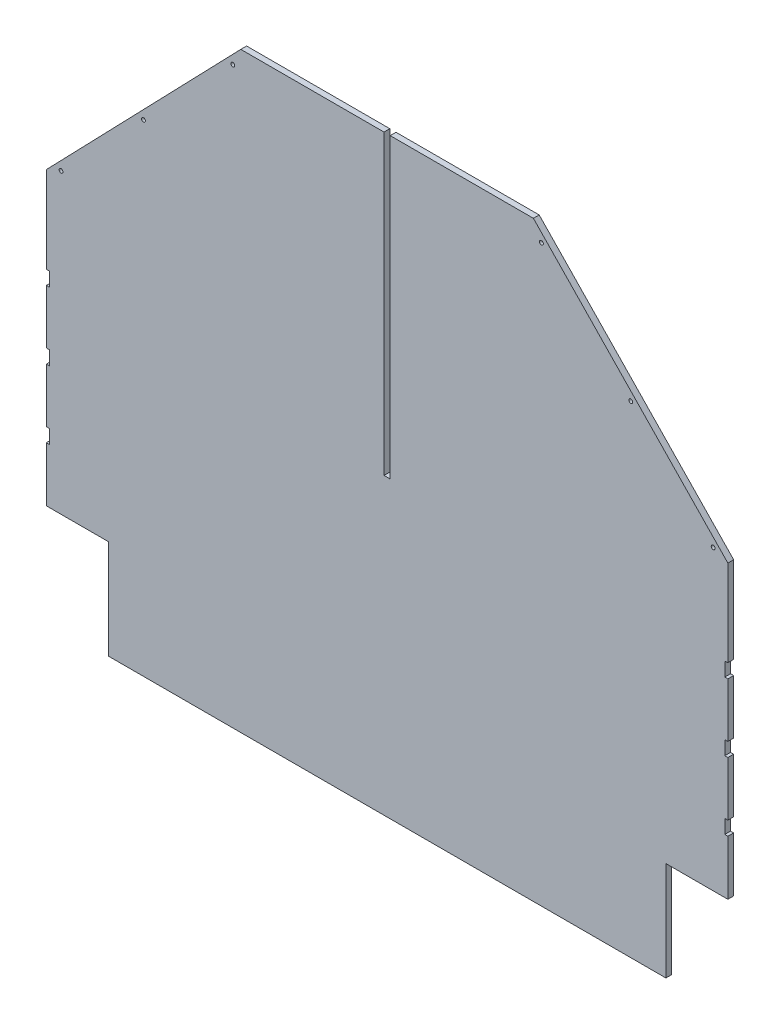
SolidWorks part; units mm, degrees
material "Pine"
ref_plane "Front Plane" through (0, 0, 0) normal (0, 0, 1) x (1, 0, 0)
ref_plane "Top Plane" through (0, 0, 0) normal (0, 1, 0) x (1, 0, 0)
ref_plane "Right Plane" through (0, 0, 0) normal (1, 0, 0) x (0, 0, -1)
sketch "Sketch1" plane through (0, 0, 0) normal (0, 0, 1) x (1, 0, 0)
  line L0 (1068.4674, -524.1043) -> (941.4674, -524.1043)
  line L1 (70.0554, 485.5457) -> (669.8794, 485.5457)
  line L2 (-328.5326, 72.7957) -> (-328.5326, -524.1043)
  line L3 (-201.5326, -727.3043) -> (941.4674, -727.3043)
  line L4 (1068.4674, 72.7957) -> (1068.4674, -524.1043)
  line L5 (-328.5326, -524.1043) -> (-201.5326, -524.1043)
  line L6 (-201.5326, -524.1043) -> (-201.5326, -727.3043)
  line L7 (369.9674, -727.3043) -> (369.9674, -138.7274) construction
  line L8 (-328.5326, -524.1043) -> (-328.5326, 72.7957) construction
  line L9 (-328.5326, 72.7957) -> (70.0554, 485.5457)
  line L10 (941.4674, -524.1043) -> (941.4674, -727.3043)
  line L11 (1068.4674, -524.1043) -> (1068.4674, 72.7957) construction
  line L12 (1068.4674, 72.7957) -> (669.8794, 485.5457)
  line L13 (369.9674, 485.5457) -> (369.9674, -138.7274) construction
  dimension "D2" = 127
  dimension "D3" = 596.9
  dimension "D4" = 127
  dimension "D5" = 596.9
  dimension "D6" = 136
  dimension "D7" = 136
extrude "Boss-Extrude1" add sketch "Sketch1" along normal blind 11.9062
sketch "Sketch2" plane through (0, 0, 11.9062) normal (0, 0, 1) x (1, 0, 0)
  line L0 (369.9674, 485.5457) -> (363.6174, 485.5457) construction
  line L1 (669.8794, 485.5457) -> (70.0554, 485.5457) construction
  line L3 (363.6174, 485.5457) -> (376.3174, 485.5457)
  line L4 (363.6174, 485.5457) -> (363.6174, -124.0543)
  line L5 (363.6174, -124.0543) -> (376.3174, -124.0543)
  line L6 (376.3174, 485.5457) -> (376.3174, -124.0543)
  dimension "D1" = 6.35
  dimension "D2" = 609.6
  dimension "D3" = 12.7
extrude "Cut-Extrude1" cut sketch "Sketch2" against normal through all contours L6 L5 L4 L3
sketch "Sketch3" plane through (0, 0, 11.9062) normal (0, 0, 1) x (1, 0, 0)
  line L0 (-328.5326, 72.7957) -> (-328.5326, -524.1043) construction
  line L1 (-328.5326, -412.1538) -> (-322.1826, -412.1538)
  line L2 (-328.5326, -412.1538) -> (-328.5326, -383.5788)
  line L3 (-328.5326, -383.5788) -> (-322.1826, -383.5788)
  line L4 (-322.1826, -412.1538) -> (-322.1826, -383.5788)
  line L6 (-328.5326, -272.4538) -> (-322.1826, -272.4538)
  line L7 (-328.5326, -272.4538) -> (-328.5326, -243.8788)
  line L8 (-328.5326, -243.8788) -> (-322.1826, -243.8788)
  line L9 (-322.1826, -272.4538) -> (-322.1826, -243.8788)
  line L10 (-328.5326, -132.7538) -> (-322.1826, -132.7538)
  line L11 (-328.5326, -132.7538) -> (-328.5326, -104.1788)
  line L12 (-328.5326, -104.1788) -> (-322.1826, -104.1788)
  line L13 (-322.1826, -132.7538) -> (-322.1826, -104.1788)
  line L14 (-322.1826, -397.8663) -> (-324.6647, -397.8663) construction
  line L15 (-322.1826, -258.1663) -> (-324.6647, -258.1663) construction
  line L16 (-322.1826, -118.4663) -> (-326.1711, -118.4663) construction
  line L17 (-328.5326, -524.1043) -> (-201.5326, -524.1043) construction
  line L18 (369.9674, -727.3043) -> (369.9674, -431.4526) construction
  line L19 (-201.5326, -727.3043) -> (941.4674, -727.3043) construction
  line L20 (1062.1174, -118.4663) -> (1066.1059, -118.4663) construction
  line L21 (1062.1174, -258.1663) -> (1064.5994, -258.1663) construction
  line L22 (1062.1174, -397.8663) -> (1064.5994, -397.8663) construction
  line L23 (1062.1174, -132.7538) -> (1062.1174, -104.1788)
  line L24 (1068.4674, -104.1788) -> (1062.1174, -104.1788)
  line L25 (1068.4674, -132.7538) -> (1068.4674, -104.1788)
  line L26 (1068.4674, -132.7538) -> (1062.1174, -132.7538)
  line L27 (1062.1174, -272.4538) -> (1062.1174, -243.8788)
  line L28 (1068.4674, -243.8788) -> (1062.1174, -243.8788)
  line L29 (1068.4674, -272.4538) -> (1068.4674, -243.8788)
  line L30 (1068.4674, -272.4538) -> (1062.1174, -272.4538)
  line L31 (1062.1174, -412.1538) -> (1062.1174, -383.5788)
  line L32 (1068.4674, -383.5788) -> (1062.1174, -383.5788)
  line L33 (1068.4674, -412.1538) -> (1068.4674, -383.5788)
  line L34 (1068.4674, -412.1538) -> (1062.1174, -412.1538)
  dimension "D1" = 28.575
  dimension "D2" = 6.35
  dimension "D3" = 126.238
  dimension "D4" = 265.938
  dimension "D5" = 405.638
extrude "Cut-Extrude3" cut sketch "Sketch3" against normal through all
hole_wizard "5/16 (0.3125) Diameter Hole1" positions "Sketch4" profile "Sketch5" hole size "5/16" standard "ANSI Inch" end condition through all
sketch "Sketch4" plane through (0, 0, 11.9062) normal (0, 0, 1) x (1, 0, 0)
  line L0 (70.0554, 485.5457) -> (-328.5326, 72.7957) construction
  line L1 (1068.4674, 72.7957) -> (669.8794, 485.5457) construction
  point P0 (686.2237, 450.3383)
  point P2 (1038.3428, 85.7083)
  point P4 (869.3395, 260.7164)
  point P6 (-298.408, 85.7083)
  point P8 (-129.4047, 260.7164)
  point P10 (53.7111, 450.3383)
  dimension "D1" = 12.7
  dimension "D2" = 12.7
  dimension "D3" = 12.7
  dimension "D4" = 12.7
  dimension "D5" = 12.7
  dimension "D6" = 12.7
sketch "Sketch5" plane through (686.2237, 450.3383, 11.9062) normal (1, 0, 0) x (0, -1, 0)
  line L0 (0, 0) -> (0, 11.9062)
  line L1 (0, 11.9062) -> (3.9687, 11.9062)
  line L2 (3.9687, 11.9062) -> (3.9687, 0)
  line L5 (3.9687, 0) -> (0, 0)
  line L11 (0, -6.35) -> (0, 107.95) construction
  dimension "Thru Hole Dia." = 7.9375
  dimension "Thru Hole Depth" = 11.9062
